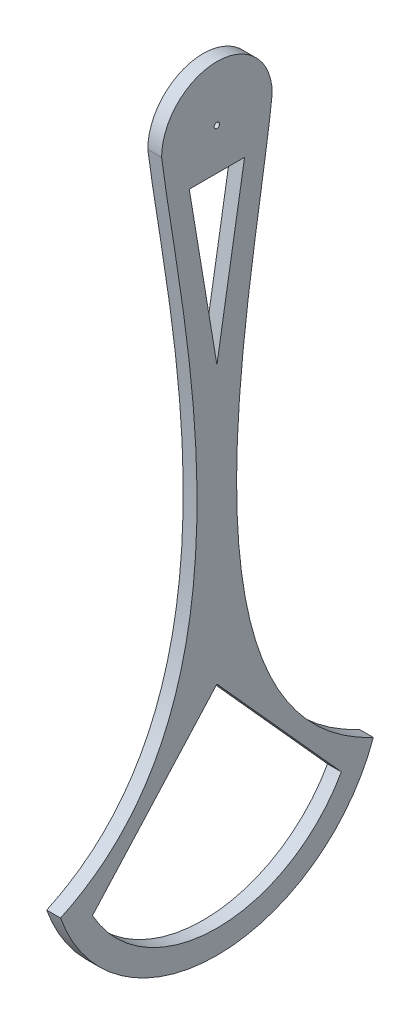
SolidWorks part; units mm, degrees
ref_plane "Plan de face" through (0, 0, 0) normal (0, 0, 1) x (1, 0, 0)
ref_plane "Plan de dessus" through (0, 0, 0) normal (0, 1, 0) x (1, 0, 0)
ref_plane "Plan de droite" through (0, 0, 0) normal (1, 0, 0) x (0, 0, -1)
sketch "Esquisse1" plane through (0, 0, 0) normal (1, 0, 0) x (0, 0, -1)
  line L0 (0, 0) -> (0, -268.6993) construction
  line L1 (-7.5, -100) -> (7.5, -100) construction
  line L2 (-73.1781, -200) -> (73.1781, -200) construction
  line L3 (-56.5685, -220) -> (56.5685, -220) construction
  line L4 (-21.7357, -200) -> (22.1576, -200) construction
  line L5 (-20, 0) -> (20, 0) construction
  line L6 (-45, -225) -> (45, -225) construction
  line L7 (45, -225) -> (0, -175)
  line L8 (0, -175) -> (-45, -225)
  line L9 (-10, -15) -> (10, -15)
  line L10 (-10, -15) -> (0, -75)
  line L11 (0, -75) -> (10, -15)
  arc A0 (20, 0) -> (-20, 0) centre (0, 0) ccw
  arc A1 (-56.5685, -220) -> (56.5685, -220) centre (0, -200) ccw
  arc A2 (-45, -225) -> (45, -225) centre (0, -200) ccw
  circle A3 centre (0, 0) radius 1
  spline S0 degree 3 poles (56.5685, -220) (-20.766, -183.9383) (14.2288, -53.4619) (20, 0) knots 0 0 0 0 1 1 1 1
  spline S1 degree 3 poles (-56.5685, -220) (19.7793, -184.8812) (-13.4618, -52.729) (-20, 0) knots 0 0 0 0 1 1 1 1
  point P6 (0, -100)
  point P15 (0, -220)
  point P21 (0, -225)
  point P25 (0, -15)
  dimension "D5" = 60
  dimension "D13" = 2
  dimension "D14" = 20
  dimension "D2" = 15
  dimension "D3" = 100
  dimension "D4" = 175
  dimension "D6" = 5
  dimension "D7" = 20
  dimension "D8" = 45
  dimension "D9" = 25
  dimension "D10" = 15
  dimension "D11" = 20
  dimension "D12" = 60
extrude "Boss.-Extru.1" add sketch "Esquisse1" along normal blind 5
sketch "Esquisse2" plane through (0, 0, 0) normal (-1, 0, 0) x (0, 0, 1)
  circle A0 centre (0, 0) radius 3
  dimension "D1" = 6
extrude "Enlèv. mat.-Extru.1" cut sketch "Esquisse2" against normal blind 2
sketch "Esquisse3" plane through (0, 0, 0) normal (-1, 0, 0) x (0, 0, 1)
  circle A0 centre (0, 0) radius 3
  circle A1 centre (0, 0) radius 10
  dimension "D1" = 20
  dimension "D2" = 6
extrude "Boss.-Extru.2" add sketch "Esquisse3" along normal blind 3
chamfer "Chanfrein1" distance 3 angle 45 1 edges at (-3, 0, 10)
